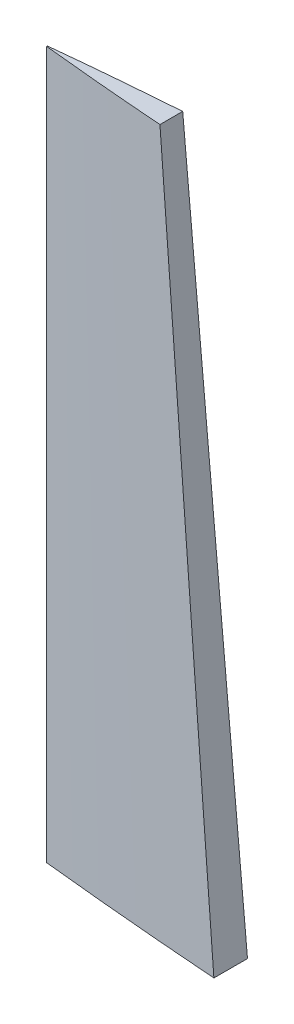
SolidWorks part; units mm, degrees
ref_plane "Front Plane" through (0, 0, 0) normal (0, 0, 1) x (1, 0, 0)
ref_plane "Top Plane" through (0, 0, 0) normal (0, 1, 0) x (1, 0, 0)
ref_plane "Right Plane" through (0, 0, 0) normal (1, 0, 0) x (0, 0, -1)
ref_plane "Plane1" through (0, 22, 0) normal (0, 1, 0) x (1, 0, 0)
sketch "Sketch1" plane through (0, 22, 0) normal (0, 1, 0) x (1, 0, 0)
  line L0 (-111.2363, 4.1237) -> (-111.2363, -4.1237)
  line L1 (-156.269, 0.1419) -> (-156.269, -0.1419)
  spline S0 degree 3 poles (-111.2363, 4.1237) (-111.4048, 4.1118) (-113.9075, 3.9352) (-118.6057, 3.5713) (-125.1704, 3.0472) (-131.2533, 2.5326) (-136.788, 2.0434) (-141.7138, 1.5898) (-145.9768, 1.183) (-149.5302, 0.8332) (-152.3351, 0.55) (-154.3609, 0.3415) (-155.5853, 0.2137) (-156.1319, 0.1563) (-156.269, 0.1419) knots 0 0 0 0 0.011212 0.166483 0.312686 0.448211 0.571563 0.681381 0.776452 0.855723 0.918312 0.963525 0.990856 1 1 1 1
  spline S1 degree 3 poles (-111.2363, -4.1237) (-111.4048, -4.1118) (-113.9075, -3.9352) (-118.6057, -3.5713) (-125.1704, -3.0472) (-131.2533, -2.5326) (-136.788, -2.0434) (-141.7138, -1.5898) (-145.9768, -1.183) (-149.5302, -0.8332) (-152.3351, -0.55) (-154.3609, -0.3415) (-155.5853, -0.2137) (-156.1319, -0.1563) (-156.269, -0.1419) knots 0 0 0 0 0.011212 0.166483 0.312686 0.448211 0.571563 0.681381 0.776452 0.855723 0.918312 0.963525 0.990856 1 1 1 1
ref_plane "Plane2" through (0, 195.337, 0) normal (0, 1, 0) x (1, 0, 0)
sketch "Sketch2" plane through (0, 195.337, 0) normal (0, 1, 0) x (1, 0, 0)
  line L0 (-125.7965, 2.7904) -> (-125.7965, -2.7904)
  line L1 (-156.269, 0.096) -> (-156.269, -0.096)
  spline S0 degree 3 poles (-125.7965, 2.7904) (-125.9106, 2.7823) (-127.6041, 2.6628) (-130.7832, 2.4166) (-135.2254, 2.062) (-139.3415, 1.7138) (-143.0867, 1.3827) (-146.4199, 1.0758) (-149.3045, 0.8005) (-151.709, 0.5638) (-153.6071, 0.3722) (-154.9778, 0.2311) (-155.8063, 0.1446) (-156.1763, 0.1057) (-156.269, 0.096) knots 0 0 0 0 0.011212 0.166483 0.312686 0.448211 0.571563 0.681381 0.776452 0.855723 0.918312 0.963525 0.990856 1 1 1 1
  spline S1 degree 3 poles (-125.7965, -2.7904) (-125.9106, -2.7823) (-127.6041, -2.6628) (-130.7832, -2.4166) (-135.2254, -2.062) (-139.3415, -1.7138) (-143.0867, -1.3827) (-146.4199, -1.0758) (-149.3045, -0.8005) (-151.709, -0.5638) (-153.6071, -0.3722) (-154.9778, -0.2311) (-155.8063, -0.1446) (-156.1763, -0.1057) (-156.269, -0.096) knots 0 0 0 0 0.011212 0.166483 0.312686 0.448211 0.571563 0.681381 0.776452 0.855723 0.918312 0.963525 0.990856 1 1 1 1
loft "Loft1" add profiles "Sketch1", "Sketch2" connector at (-111.2363, 22, -4.1237) connector at (-125.7965, 195.337, -2.7904)
